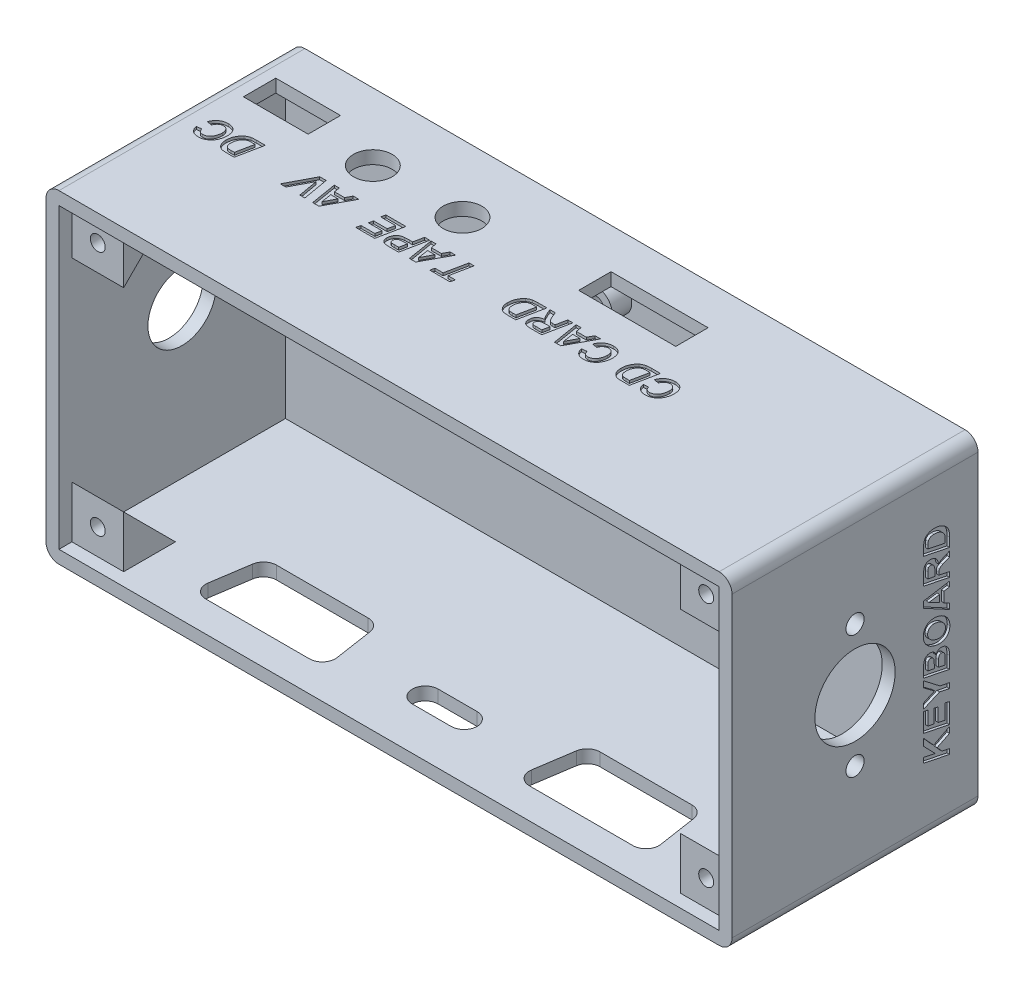
SolidWorks part; units mm, degrees
material "ABS"
ref_plane "Спереди" through (0, 0, 0) normal (0, 0, 1) x (1, 0, 0)
ref_plane "Сверху" through (0, 0, 0) normal (0, 1, 0) x (1, 0, 0)
ref_plane "Справа" through (0, 0, 0) normal (1, 0, 0) x (0, 0, -1)
sketch "Эскиз1" plane through (0, 0, 0) normal (0, 0, 1) x (1, 0, 0)
  line L1 (-53, -25) -> (53, -25)
  line L2 (-53, -25) -> (-53, 25)
  line L3 (-53, 25) -> (53, 25)
  line L4 (53, -25) -> (53, 25)
  line L5 (-53, -25) -> (53, 25) construction
  line L6 (-53, 25) -> (53, -25) construction
  point P0 (0, 0)
  dimension "D1" = 106
  dimension "D2" = 50
extrude "CaseBody" add sketch "Эскиз1" along normal blind 3
sketch "Эскиз2" plane through (0, 0, 3) normal (0, 0, 1) x (1, 0, 0)
  line L0 (53, 25) -> (-53, 25) construction
  line L1 (-51, -23) -> (51, -23)
  line L2 (-51, -23) -> (-51, 23)
  line L3 (-51, 23) -> (51, 23)
  line L4 (51, -23) -> (51, 23)
  line L5 (-51, -23) -> (51, 23) construction
  line L6 (-51, 23) -> (51, -23) construction
  line L7 (53, -25) -> (53, 25) construction
  line L9 (-53, -25) -> (53, -25)
  line L10 (-53, -25) -> (-53, 25)
  line L11 (-53, 25) -> (53, 25)
  line L12 (53, -25) -> (53, 25)
  line L13 (-53, -25) -> (53, 25) construction
  line L14 (-53, 25) -> (53, -25) construction
  point P0 (0, 0)
  point P10 (0, 0)
  dimension "D1" = 2
  dimension "D2" = 2
extrude "CaseBody2" add sketch "Эскиз2" along normal blind 35
sketch "Эскиз3" plane through (0, 0, 3) normal (0, 0, 1) x (1, 0, 0)
  line L0 (51, 23) -> (-51, 23) construction
  line L1 (-46.625, 1.53) -> (46.625, 1.53) construction
  line L2 (-46.625, 1.53) -> (-46.625, 19.18) construction
  line L3 (-46.625, 19.18) -> (46.625, 19.18) construction
  line L4 (46.625, 1.53) -> (46.625, 19.18) construction
  line L5 (-46.625, 1.53) -> (46.625, 19.18) construction
  line L6 (-46.625, 19.18) -> (46.625, 1.53) construction
  circle A0 centre (-46.625, 1.53) radius 2.5
  circle A1 centre (46.625, 1.53) radius 2.5
  circle A2 centre (0.005, 19.18) radius 2.5
  point P0 (0, 0)
  point P13 (0, 10.355)
  dimension "D4" = 5
  dimension "D1" = 93.25
  dimension "D2" = 17.65
  dimension "D3" = 46.63
  dimension "D5" = 3.82
extrude "SizifXXSFix" add sketch "Эскиз3" along normal blind 3
sketch "Эскиз4" plane through (0, 0, 6) normal (0, 0, 1) x (1, 0, 0)
  circle A0 centre (-46.625, 1.53) radius 1.2
  circle A1 centre (0.005, 19.18) radius 1.2
  circle A2 centre (46.625, 1.53) radius 1.2
  dimension "D1" = 2.4
extrude "Holes2_5" cut sketch "Эскиз4" against normal blind 5.6
sketch "Эскиз5" plane through (0, 25, 0) normal (0, 1, 0) x (1, 0, 0)
  line L1 (-49.3, -6.2) -> (-39.3, -6.2)
  line L2 (-49.3, -6.2) -> (-49.3, -11.2)
  line L3 (-49.3, -11.2) -> (-39.3, -11.2)
  line L4 (-39.3, -6.2) -> (-39.3, -11.2)
  line L5 (-49.3, -6.2) -> (-39.3, -11.2) construction
  line L6 (-49.3, -11.2) -> (-39.3, -6.2) construction
  line L7 (2.5, -6.2) -> (17.5, -6.2)
  line L8 (2.5, -6.2) -> (2.5, -11.2)
  line L9 (2.5, -11.2) -> (17.5, -11.2)
  line L10 (17.5, -6.2) -> (17.5, -11.2)
  line L11 (2.5, -6.2) -> (17.5, -11.2) construction
  line L12 (2.5, -11.2) -> (17.5, -6.2) construction
  line L13 (53, 0) -> (-53, 0) construction
  line L14 (-53, -38) -> (-53, 0) construction
  circle A0 centre (-30.1, -10.4) radius 3
  circle A1 centre (-16.25, -10.4) radius 3
  point P0 (-44.3, -8.7)
  point P9 (10, -8.7)
  dimension "D5" = 6
  dimension "D2" = 10
  dimension "D3" = 6.2
  dimension "D4" = 5
  dimension "D6" = 13.85
  dimension "D7" = 14.2
  dimension "D8" = 26.25
  dimension "D9" = 10.4
  dimension "D10" = 5
  dimension "D11" = 15
  dimension "D12" = 22.9
extrude "SizifXXS_Holes" cut sketch "Эскиз5" against normal up to next
sketch "Эскиз7" plane through (53, 0, 0) normal (1, 0, 0) x (0, 0, -1)
  line L0 (-20, 0) -> (-6.0564, 0) construction
  line L2 (0, -25) -> (0, 25) construction
  circle A0 centre (-19, 0) radius 6.2
  circle A1 centre (-19, -9.5) radius 1.4
  circle A2 centre (-19, 9.5) radius 1.4
  dimension "D1" = 12.4
  dimension "D4" = 2.8
  dimension "D2" = 19
  dimension "D3" = 19
extrude "PS2Hole" cut sketch "Эскиз7" against normal up to next
sketch "Эскиз8" plane through (51, 0, 0) normal (-1, 0, 0) x (0, 0, 1)
  line L0 (36, 23) -> (36, 15)
  line L1 (38, 23) -> (3, 23) construction
  line L2 (36, 15) -> (28, 23)
  line L3 (28, 23) -> (36, 23)
  line L4 (38, -23) -> (38, 23) construction
  dimension "D1" = 8
  dimension "D2" = 8
  dimension "D3" = 2
extrude "CaseTopFix" add sketch "Эскиз8" along normal blind 8
sketch "Эскиз9" plane through (0, 0, 36) normal (0, 0, 1) x (1, 0, 0)
  line L0 (43, 15) -> (43, 23) construction
  line L1 (43, 23) -> (51, 23) construction
  line L2 (43, 23) -> (43, 15) construction
  line L3 (43, 15) -> (51, 15) construction
  line L4 (51, 23) -> (51, 15) construction
  line L5 (43, 23) -> (51, 15) construction
  line L6 (43, 15) -> (51, 23) construction
  line L7 (43, 23) -> (51, 23) construction
  circle A0 centre (47, 19) radius 1.15
  point P0 (47, 19)
  dimension "D1" = 2.3
extrude "CaseTopHoles" cut sketch "Эскиз9" against normal up to next
mirror "CaseTopHoles1" about plane through (0, 0, 0) normal (0, 1, 0) of "CaseTopHoles", "CaseTopFix"
mirror "CaseTopHoles2" about plane through (0, 0, 0) normal (1, 0, 0) of "CaseTopHoles", "CaseTopHoles1", "CaseTopFix"
fillet "Fillet" radius 2 4 edges at (-53, 25, 19) (53, 25, 19) (53, -25, 19) (-53, -25, 19)
sketch "Эскиз10" plane through (0, 25, 0) normal (0, 1, 0) x (1, 0, 0)
  line L0 (51, 0) -> (-51, 0) construction
  line L1 (-53, -38) -> (-53, 0) construction
  text T0 "<r180>VA</r>" font "Times New Roman" height 4
  text T1 "<r180>EPAT</r>" font "Times New Roman" height 4
  text T2 "<r180>CD</r>" font "Times New Roman" height 4
  text T3 "<r180>DRAC DC</r>" font "Times New Roman" height 4
  dimension "D1" = 16
  dimension "D2" = 22.5962
  dimension "D3" = 11.2585
  dimension "D4" = 14.4528
  dimension "D5" = 21.8
extrude "InterfaceInfo" cut sketch "Эскиз10" against normal blind 0.4
sketch "Эскиз11" plane through (53, 0, 0) normal (1, 0, 0) x (0, 0, -1)
  line L0 (-4.4, -15.5) -> (-4.4, 15.5) construction
  line L1 (0, -23) -> (0, 23) construction
  text T0 "KEYBOARD" font "Arial" height 4
  point P0 (-4.4, 0)
  dimension "D1" = 4.4
  dimension "D2" = 31
extrude "PS2Info" cut sketch "Эскиз11" against normal blind 0.4
sketch "Эскиз12" plane through (0, 23, 0) normal (0, -1, 0) x (1, 0, 0)
  line L1 (-53, 0) -> (-53, 38) construction
  line L2 (-51, 0) -> (51, 0) construction
  text T0 "© Peter Ukhov 2023" font "Arial" height 6
  dimension "D1" = 16
  dimension "D2" = 14
sketch "Эскиз13" plane through (-53, 0, 0) normal (-1, 0, 0) x (0, 0, 1)
  line L1 (0, 23) -> (0, -23) construction
  circle A0 centre (19, 0) radius 5.25
  dimension "D1" = 10.5
  dimension "D2" = 19
extrude "ButtonHole" cut sketch "Эскиз13" against normal up to next
sketch "Эскиз14" plane through (-53, 0, 0) normal (-1, 0, 0) x (0, 0, 1)
  line L0 (6.2274, 10.1387) -> (6.2274, -12.1287) construction
  text T0 "POWER" font "Arial" height 4
extrude "ButtonInfo" cut sketch "Эскиз14" against normal blind 0.4
extrude "CopyLeft" cut sketch "Эскиз12" against normal blind 0.4
sketch "Эскиз15" plane through (0, -25, 0) normal (0, -1, 0) x (1, 0, 0)
  line L0 (-3, 29.4) -> (3, 29.4) construction
  line L1 (-3, 31.4) -> (3, 31.4)
  line L2 (-3, 27.4) -> (3, 27.4)
  line L3 (-51, 38) -> (51, 38) construction
  arc A0 (-3, 31.4) -> (-3, 27.4) centre (-3, 29.4) ccw
  arc A1 (3, 27.4) -> (3, 31.4) centre (3, 29.4) ccw
  point P2 (0, 29.4)
  dimension "D1" = 4
  dimension "D2" = 6
  dimension "D3" = 8.6
extrude "USBArduinoNano" cut sketch "Эскиз15" against normal up to next
sketch "Эскиз16" plane through (0, -25, 0) normal (0, -1, 0) x (1, 0, 0)
  line L0 (-34.9772, 31.0017) -> (-34.064, 25.0017)
  line L1 (-32.0868, 23.3026) -> (-17.9132, 23.3026)
  line L2 (-15.936, 25.0017) -> (-15.0228, 31.0017)
  line L3 (-17, 33.3026) -> (-33, 33.3026)
  line L4 (-33, 33.3026) -> (-17.9132, 23.3026) construction
  line L5 (-32.0868, 23.3026) -> (-17, 33.3026) construction
  line L6 (-51, 38) -> (51, 38) construction
  arc A0 (-15.0228, 31.0017) -> (-17, 33.3026) centre (-17, 31.3026) ccw
  arc A1 (-33, 33.3026) -> (-34.9772, 31.0017) centre (-33, 31.3026) ccw
  arc A2 (-17.9132, 23.3026) -> (-15.936, 25.0017) centre (-17.9132, 25.3026) ccw
  arc A3 (-34.064, 25.0017) -> (-32.0868, 23.3026) centre (-32.0868, 25.3026) ccw
  point P0 (-25, 28)
  dimension "D1" = 2
  dimension "D2" = 2
  dimension "D3" = 25
  dimension "D4" = 10
  dimension "D5" = 16
  dimension "D7" = 10
  dimension "D8" = 81.346
  dimension "D9" = 81.346
extrude "NESCut1" cut sketch "Эскиз16" against normal up to next
mirror "NESCut2" about plane through (0, 0, 0) normal (1, 0, 0) of "NESCut1"
equation "\"D1@Эскиз1\"=100+2*2+2"
equation "\"D5@Эскиз3\"=3.42+0.4"
equation "\"D2@Эскиз15\"=10-2-2"
equation "\"12ю5\"=12"
